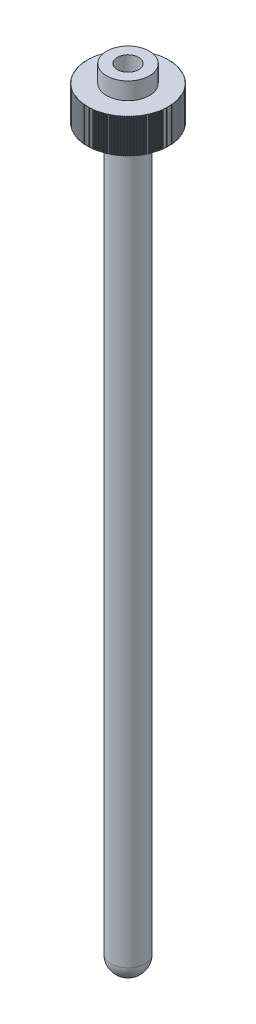
SolidWorks part; units mm, degrees
material "1.4000 (X6Cr13)"
ref_plane "Alzado" through (0, 0, 0) normal (0, 0, 1) x (1, 0, 0)
ref_plane "Planta" through (0, 0, 0) normal (0, 1, 0) x (1, 0, 0)
ref_plane "Vista lateral" through (0, 0, 0) normal (1, 0, 0) x (0, 0, -1)
sketch "Croquis1" plane through (0, 0, 0) normal (0, 0, 1) x (1, 0, 0)
  line L0 (0, 0) -> (0, 184)
  line L1 (0, 184) -> (5, 184)
  line L2 (5, 184) -> (5, 180)
  line L3 (5, 180) -> (9.5, 180)
  line L4 (9.5, 180) -> (9.5, 172)
  line L5 (9.5, 172) -> (4, 172)
  line L6 (4, 172) -> (4, 0)
  line L7 (4, 0) -> (0, 0)
  dimension "D1" = 4
  dimension "D2" = 184
  dimension "D3" = 4
  dimension "D4" = 8
  dimension "D5" = 9.5
  dimension "D6" = 5
revolve "Revolución1" add sketch "Croquis1" angle 360 about L0
fillet "Redondeo1" radius 4 1 edges at (0, 0, -4)
sketch "Croquis3" plane through (0, 184, 0) normal (0, 1, 0) x (1, 0, 0)
  circle A0 centre (0, 0) radius 2.5
  dimension "D1" = 5
extrude "Cortar-Extruir1" cut sketch "Croquis3" against normal blind 32
sketch "Croquis4" plane through (0, 180, 0) normal (0, 1, 0) x (1, 0, 0)
  line L0 (0, 10.0874) -> (0, 8.6961) construction
  line L1 (-0.1332, 9.4991) -> (0, 9.3659)
  line L2 (0, 9.3659) -> (0.3668, 9.7327)
  line L3 (-0.1332, 9.4991) -> (0.1608, 9.5267)
  circle A0 centre (0, 0) radius 9.5 construction
  circle M3 centre (0, 0) radius 9.5
  dimension "D1" = 0.5
extrude "Cortar-Extruir2" cut sketch "Croquis4" against normal blind 32 contours L0 L2 M3 | L0 L1 M3 region at (0.0445, 180, -9.4551) region at (-0.0445, 180, -9.4551)
pattern_circular "MatrizC1" count 200 over 360 about axis through (0, 0, 0) along (0, -1, 0) of "Cortar-Extruir2"
